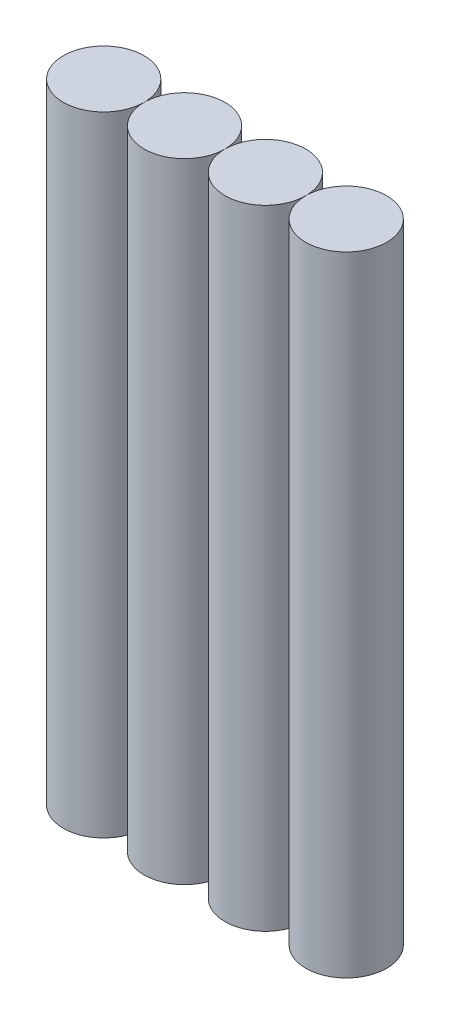
SolidWorks part; units mm, degrees
ref_plane "Front Plane" through (0, 0, 0) normal (0, 0, 1) x (1, 0, 0)
ref_plane "Top Plane" through (0, 0, 0) normal (0, 1, 0) x (1, 0, 0)
ref_plane "Right Plane" through (0, 0, 0) normal (1, 0, 0) x (0, 0, -1)
sketch "Sketch1" plane through (0, 0, 0) normal (0, 1, 0) x (1, 0, 0)
  line L0 (0, 0) -> (54, 0) construction
  circle A0 centre (0, 0) radius 9
  circle A1 centre (18, 0) radius 9
  circle A2 centre (36, 0) radius 9
  circle A3 centre (54, 0) radius 9
  point P9 (140.4775, 0)
  point P10 (58.59, 0)
  point P11 (49.0252, 0)
  point P12 (86.5471, 0)
  point P13 (131.1243, 0)
  dimension "D1" = 18
extrude "Boss-Extrude1" add sketch "Sketch1" along normal blind 140 contours A1 L0 | L0 A1 | A0 | A2 L0 | L0 A2 | A3 region at (18, 0, -3.8197) region at (-8.7454, 0, 0) region at (54, 0, -8.7454) region at (36, 0, -3.8197) region at (36, 0, 3.8197) region at (18, 0, 3.8197)
